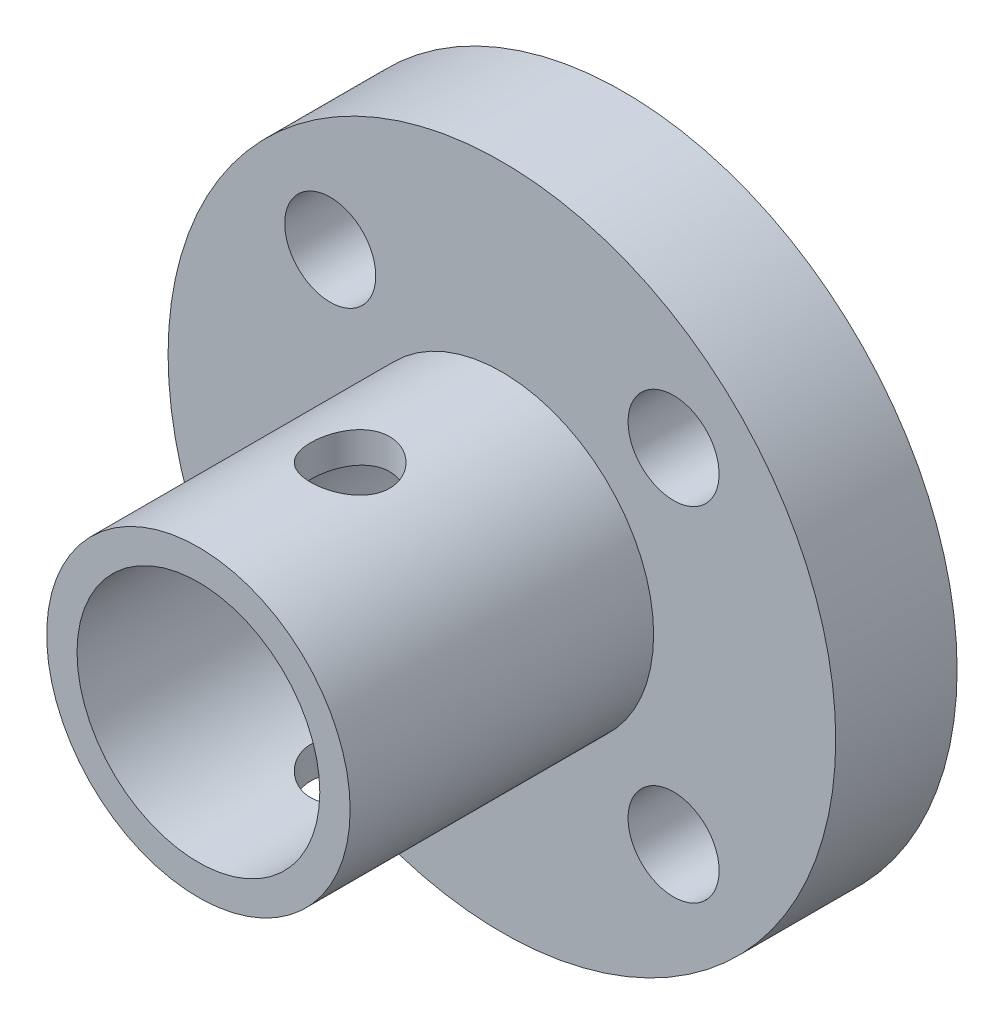
SolidWorks part; units mm, degrees
ref_plane "Front Plane" through (0, 0, 0) normal (0, 0, 1) x (1, 0, 0)
ref_plane "Top Plane" through (0, 0, 0) normal (0, 1, 0) x (1, 0, 0)
ref_plane "Right Plane" through (0, 0, 0) normal (1, 0, 0) x (0, 0, -1)
sketch "Sketch1" plane through (0, 0, 0) normal (0, 0, 1) x (1, 0, 0)
  line L0 (0, 0) -> (0, 11) construction
  line L1 (0, 11) -> (0, 0) construction
  line L2 (0, 0) -> (-11, 0) construction
  line L3 (0, 0) -> (-7.7782, 7.7782) construction
  circle A0 centre (0, 0) radius 4
  circle A1 centre (0, 0) radius 11
  circle A2 centre (-5.6569, 5.6569) radius 1.5
  circle A3 centre (5.6569, 5.6569) radius 1.5
  circle A4 centre (5.6569, -5.6569) radius 1.5
  circle A5 centre (-5.6569, -5.6569) radius 1.5
  dimension "D1" = 8
  dimension "D2" = 22
  dimension "D3" = 3
  dimension "D4" = 8
extrude "Boss-Extrude1" add sketch "Sketch1" along normal blind 4
sketch "Sketch2" plane through (0, 0, 4) normal (0, 0, 1) x (1, 0, 0)
  circle A1 centre (0, 0) radius 4
  circle A2 centre (0, 0) radius 5
  dimension "D1" = 10
  dimension "D2" = 8
extrude "Boss-Extrude2" add sketch "Sketch2" along normal blind 10
sketch "Sketch3" plane through (0, 0, 0) normal (0, 1, 0) x (1, 0, 0)
  line L0 (0, -4) -> (0, -22.7914) construction
  line L1 (-5, -4) -> (5, -4) construction
  line L2 (-5, -14) -> (11.7824, -14) construction
  circle A0 centre (0, -9) radius 1.3019
  dimension "D1" = 5
extrude "Cut-Extrude1" cut sketch "Sketch3" against normal through all both and the other way through all
